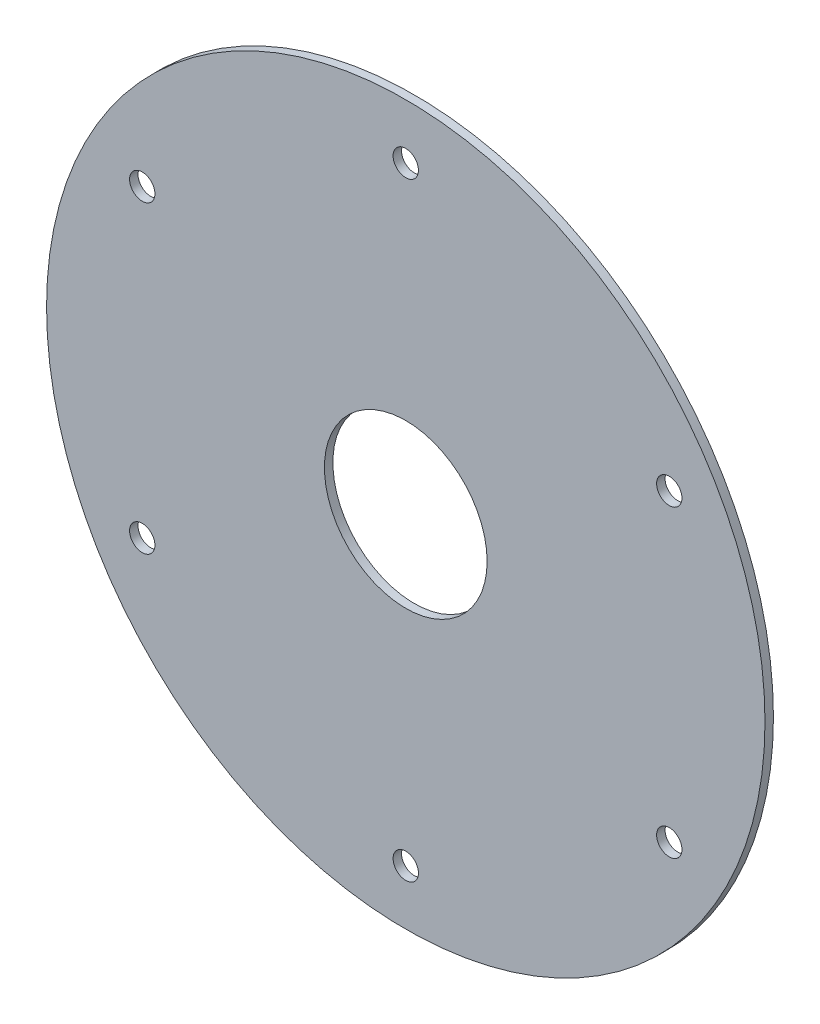
SolidWorks part; units mm, degrees
material "СТ3КП"
ref_plane "Спереди" through (0, 0, 0) normal (0, 0, 1) x (1, 0, 0)
ref_plane "Сверху" through (0, 0, 0) normal (0, 1, 0) x (1, 0, 0)
ref_plane "Справа" through (0, 0, 0) normal (1, 0, 0) x (0, 0, -1)
sketch "Эскиз1" plane through (0, 0, 0) normal (0, 0, 1) x (1, 0, 0)
  line L0 (0, 0) -> (0, 150) construction
  line L1 (0, 0) -> (0, 144) construction
  line L2 (0, 0) -> (124.7077, 72) construction
  line L3 (124.7077, 72) -> (0, 144) construction
  circle A0 centre (0, 0) radius 170
  circle A1 centre (0, 0) radius 38.5 construction
  circle A2 centre (0, 0) radius 38.5
  circle A3 centre (0, 144) radius 6
  circle A4 centre (124.7077, 72) radius 6
  circle A5 centre (124.7077, -72) radius 6
  circle A6 centre (0, -144) radius 6
  circle A7 centre (-124.7077, -72) radius 6
  circle A8 centre (-124.7077, 72) radius 6
  point P25 (0, 0)
  dimension "D1" = 6
base flange "Базовая кромка1" sketch "Эскиз1" thickness 4 reverse thickness direction yes parameters "D1"=1.5
sketch "Сгиб-Линии1" [suppressed] plane through (0, 0, 0) normal (0, 1, 0) x (1, 0, 0)
sketch "Граничная рамка1" [suppressed] plane through (0, 0, 0) normal (0, 1, 0) x (1, 0, 0)
sheet metal parameters "Листовой металл3" thickness 4 parameters "D1"=1.5
flat pattern "Развертка3" [suppressed]
sketch "Сгиб-Линии2" plane through (0, 0, 0) normal (0, 1, 0) x (1, 0, 0)
sketch3d "Граничная рамка2" [suppressed]
  line L0 (-169.9457, 170.0543, 0) -> (-170.0543, -169.9457, 0) construction
  line L1 (170.0542, 169.9457, 0) -> (169.9456, -170.0543, 0) construction
  line L2 (-169.9457, 170.0543, 0) -> (170.0542, 169.9457, 0) construction
  line L3 (-170.0543, -169.9457, 0) -> (169.9456, -170.0543, 0) construction
